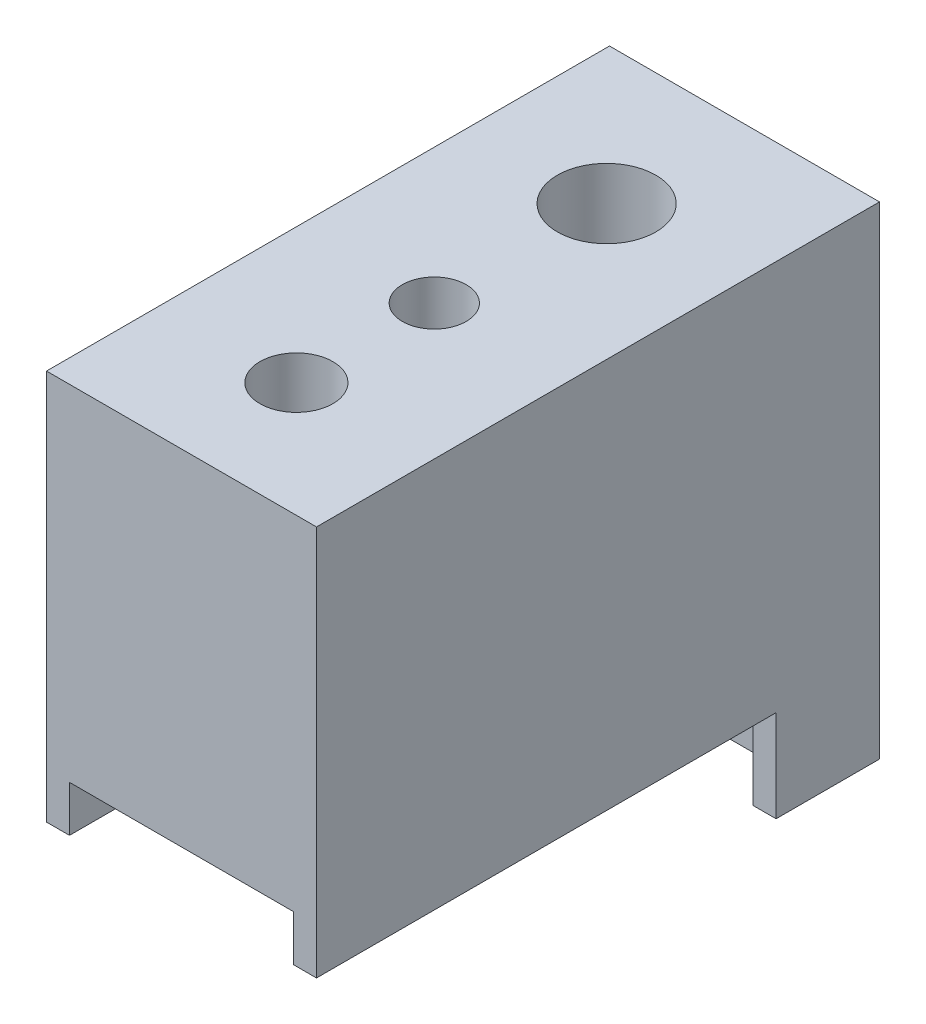
SolidWorks part; units mm, degrees
ref_plane "Front Plane" through (0, 0, 0) normal (0, 0, 1) x (1, 0, 0)
ref_plane "Top Plane" through (0, 0, 0) normal (0, 1, 0) x (1, 0, 0)
ref_plane "Right Plane" through (0, 0, 0) normal (1, 0, 0) x (0, 0, -1)
sketch "Sketch2" plane through (0, 0, 0) normal (1, 0, 0) x (0, 0, -1)
  line L0 (-44, 0) -> (0, 0)
  line L1 (0, 0) -> (0, -12)
  line L2 (-44, 0) -> (-44, 30)
  line L3 (-44, 30) -> (5, 30)
  line L4 (5, 30) -> (5, -12)
  line L5 (5, -12) -> (0, -12)
  dimension "D1" = 12
  dimension "D2" = 44
  dimension "D3" = 5
  dimension "D4" = 30
extrude "Boss-Extrude1" add sketch "Sketch2" along normal mid plane 19.5
sketch "Sketch3" plane through (9.75, 0, 0) normal (1, 0, 0) x (0, 0, -1)
  line L0 (-44, 30) -> (-44, -4)
  line L1 (-44, -4) -> (-4, -4)
  line L2 (-4, -4) -> (-4, -12)
  line L3 (-4, -12) -> (5, -12)
  line L6 (-44, 30) -> (5, 30)
  line L7 (5, 30) -> (5, -12)
  line L8 (0, 0) -> (0, -12) construction
  line L9 (-44, 0) -> (0, 0) construction
  dimension "D1" = 4
  dimension "D2" = 4
extrude "Boss-Extrude2" add sketch "Sketch3" along normal blind 2
mirror "Mirror1" about plane through (0, 0, 0) normal (1, 0, 0) of "Boss-Extrude2"
sketch "Sketch4" plane through (0, 0, 0) normal (0, -1, 0) x (1, 0, 0)
  line L0 (0, 0) -> (0, 7) construction
  line L1 (9.75, 0) -> (-9.75, 0) construction
  line L2 (0, 7) -> (0, 22) construction
  line L3 (0, 22) -> (0, 34) construction
  circle A0 centre (0, 34) radius 3.175
  circle A1 centre (0, 22) radius 2.78
  circle A2 centre (0, 7) radius 4.285
  dimension "D1" = 6.35
  dimension "D5" = 5.56
  dimension "D6" = 8.57
  dimension "D2" = 7
  dimension "D3" = 15
  dimension "D4" = 12
extrude "Cut-Extrude1" cut sketch "Sketch4" against normal through all
sketch "Sketch5" plane through (0, 0, 0) normal (0, 0, 1) x (1, 0, 0)
  line L0 (0, -7) -> (0, -12) construction
  line L1 (9.75, -12) -> (-9.75, -12) construction
  circle A0 centre (0, -7) radius 1.5
  dimension "D2" = 3
  dimension "D1" = 5
extrude "Cut-Extrude2" cut sketch "Sketch5" against normal through all
